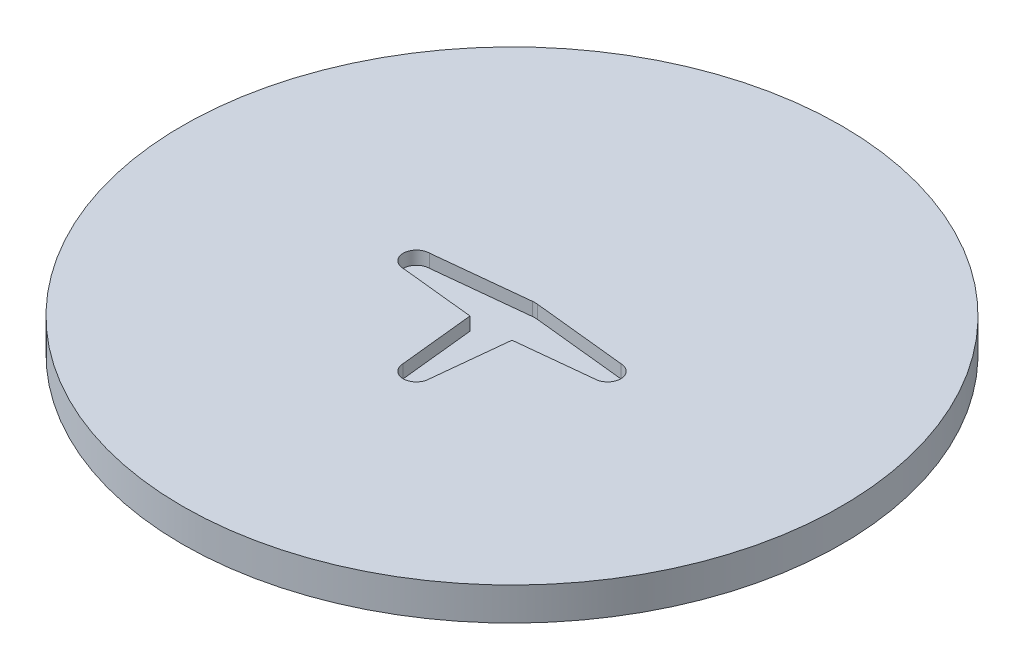
SolidWorks part; units mm, degrees
ref_plane "Front Plane" through (0, 0, 0) normal (0, 0, 1) x (1, 0, 0)
ref_plane "Top Plane" through (0, 0, 0) normal (0, 1, 0) x (1, 0, 0)
ref_plane "Right Plane" through (0, 0, 0) normal (1, 0, 0) x (0, 0, -1)
sketch "Sketch1" plane through (0, 0, 0) normal (0, 1, 0) x (1, 0, 0)
  circle A0 centre (0, 0) radius 50
  dimension "D1" = 100
extrude "Boss-Extrude1" add sketch "Sketch1" along normal blind 5
sketch "Sketch2" plane through (0, 5, 0) normal (0, 1, 0) x (1, 0, 0)
  line L1 (14.5, 2) -> (0.3647, 3.4809)
  line L2 (14.5, -2) -> (3.1854, -3.1854)
  line L3 (2, -14.5) -> (3.1854, -3.1854)
  line L4 (-2, -14.5) -> (-3.1854, -3.1854)
  line L5 (-14.5, -2) -> (-3.1854, -3.1854)
  line L6 (-14.5, 2) -> (-0.3647, 3.4809)
  arc A1 (14.5, -2) -> (14.5, 2) centre (14.5, 0) ccw
  arc A9 (-2, -14.5) -> (2, -14.5) centre (0, -14.5) ccw
  arc A10 (-14.5, 2) -> (-14.5, -2) centre (-14.5, 0) ccw
  arc A11 (0.3647, 3.4809) -> (-0.3647, 3.4809) centre (0, 0) ccw
  point P18 (0, 0)
  point P23 (0, 0)
  point P24 (0, 0)
  point P38 (0, 0)
  dimension "D2" = 4
  dimension "D3" = 3
extrude "Cut-Extrude1" cut sketch "Sketch2" against normal blind 2
sketch "Sketch3" plane through (0, 0, 0) normal (0, -1, 0) x (1, 0, 0)
  ellipse E0 centre (0, 0) end of major axis (0, -25) minor radius 7.5 (7.1837, 7.1837) -> (-7.1837, 7.1837) ccw
  ellipse E1 centre (0, 0) end of major axis (-25, 0) minor radius 7.5 (7.1837, -7.1837) -> (7.1837, 7.1837) ccw
  ellipse E2 centre (0, 0) end of major axis (0, -25) minor radius 7.5 (-7.1837, -7.1837) -> (7.1837, -7.1837) ccw
  ellipse E3 centre (0, 0) end of major axis (-25, 0) minor radius 7.5 (-7.1837, 7.1837) -> (-7.1837, -7.1837) ccw
  point P15 (0, 0)
extrude "Cut-Extrude3" cut sketch "Sketch3" against normal blind 2.5
sketch "Sketch4" plane through (0, 2.5, 0) normal (0, -1, 0) x (1, 0, 0)
  arc A0 (25, 0) -> (17.6777, 17.6777) centre (0, 0) ccw
  arc A1 (0, 25) -> (-17.6777, 17.6777) centre (0, 0) ccw
  arc A2 (-25, 0) -> (-17.6777, -17.6777) centre (0, 0) ccw
  arc A3 (0, -25) -> (17.6777, -17.6777) centre (0, 0) ccw
  ellipse E0 centre (0, 0) end of major axis (0, -25) minor radius 7.5 (6.0742, 14.6644) -> (0, 25) ccw
  ellipse E1 centre (0, 0) end of major axis (-25, 0) minor radius 7.5 (14.6644, -6.0742) -> (25, 0) ccw
  ellipse E2 centre (0, 0) end of major axis (0, -25) minor radius 7.5 (-6.0742, -14.6644) -> (0, -25) ccw
  ellipse E3 centre (0, 0) end of major axis (-25, 0) minor radius 7.5 (-14.6644, 6.0742) -> (-25, 0) ccw
  ellipse E4 centre (0, 0) end of major axis (-17.6777, -17.6777) minor radius 7.5 (17.6777, 17.6777) -> (6.0742, 14.6644) ccw
  ellipse E5 centre (0, 0) end of major axis (-17.6777, 17.6777) minor radius 7.5 (-17.6777, 17.6777) -> (-14.6644, 6.0742) ccw
  ellipse E6 centre (0, 0) end of major axis (-17.6777, -17.6777) minor radius 7.5 (-17.6777, -17.6777) -> (-6.0742, -14.6644) ccw
  ellipse E7 centre (0, 0) end of major axis (-17.6777, 17.6777) minor radius 7.5 (17.6777, -17.6777) -> (14.6644, -6.0742) ccw
  point P15 (0, 0)
  point P47 (0, 0)
extrude "Cut-Extrude4" cut sketch "Sketch4" along normal blind 1.5
sketch "Sketch5" plane through (0, 2.5, 0) normal (0, -1, 0) x (1, 0, 0)
  circle A0 centre (0, 0) radius 2.5
extrude "Boss-Extrude2" add sketch "Sketch5" along normal up to surface (2.5 mm away) up to face at (0, 0, 0)
